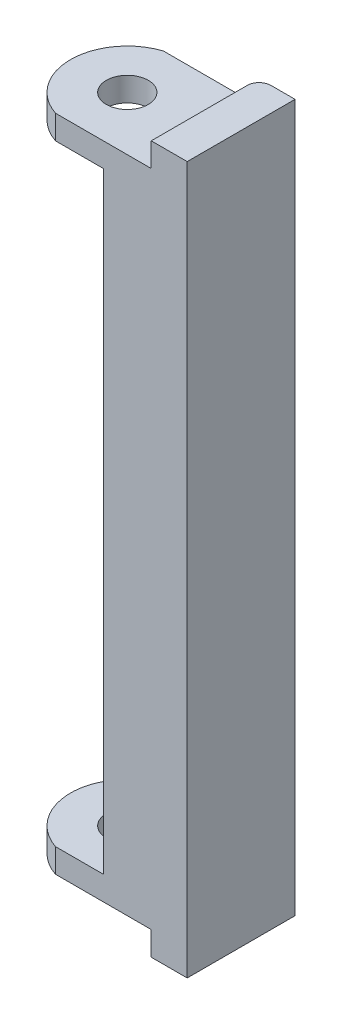
SolidWorks part; units mm, degrees
ref_plane "Front Plane" through (0, 0, 0) normal (0, 0, 1) x (1, 0, 0)
ref_plane "Top Plane" through (0, 0, 0) normal (0, 1, 0) x (1, 0, 0)
ref_plane "Right Plane" through (0, 0, 0) normal (1, 0, 0) x (0, 0, -1)
sketch "Sketch1" plane through (0, 0, 0) normal (0, 1, 0) x (1, 0, 0)
  line L0 (-2.5, 0) -> (2.5, 0) construction
  line L5 (-3.991, 4.5) -> (4, 4.5)
  line L6 (-3.991, -4.5) -> (4, -4.5)
  line L8 (7, -4.5) -> (7, 4.5)
  line L10 (5, 4.5) -> (4, 4.5)
  line L11 (7, -4.5) -> (4, -4.5)
  line L12 (7, -4.5) -> (7, 4.5)
  line L13 (7, 4.5) -> (5, 4.5)
  line L14 (4, -4.5) -> (4, 3.5)
  arc A1 (-3.991, 4.5) -> (-3.991, -4.5) centre (-2.5, 0) ccw
  circle A3 centre (-2.5, 0) radius 1.75
  arc A4 (0.0045, 4.5) -> (0.0045, -4.5) centre (-2.5, 0) cw
  arc A5 (5, 4.5) -> (4, 3.5) centre (5, 3.5) ccw
  point P2 (0, 0)
  dimension "D2" = 9.5
  dimension "D3" = 3.5
  dimension "D6" = 5.15
  dimension "D8" = 1
  dimension "D1" = 9
  dimension "D4" = 5
  dimension "D7" = 3
extrude "Boss-Extrude3" add sketch "Sketch1" along normal blind 2 contours A4 L5 A1 L6 A3 | L5 A4 L6 | L12 L11 L14 A5 L13 region at (-1.9933, 0, -4.3663) region at (2.8287, 0, -0.0477)
extrude "Boss-Extrude4" add sketch "Sketch1<3>" against normal blind 25.5 contours L5 A4 L6 | L12 L11 L14 A5 L13 region at (2.8287, 0, -0.0477)
sketch "Sketch1<3>" plane through (0, 0, 0) normal (0, 1, 0) x (1, 0, 0) same geometry as "Sketch1"
extrude "Boss-Extrude5" add sketch "Sketch1<5>" along normal blind 4 contours L13 A5 L14 L11 L8 region at (5.5102, 0, 0.0343)
sketch "Sketch1<5>" plane through (0, 0, 0) normal (0, 1, 0) x (1, 0, 0) same geometry as "Sketch1"
mirror "Mirror1" about plane through (0, -25.5, 0) normal (0, 1, 0) of bodies 111
